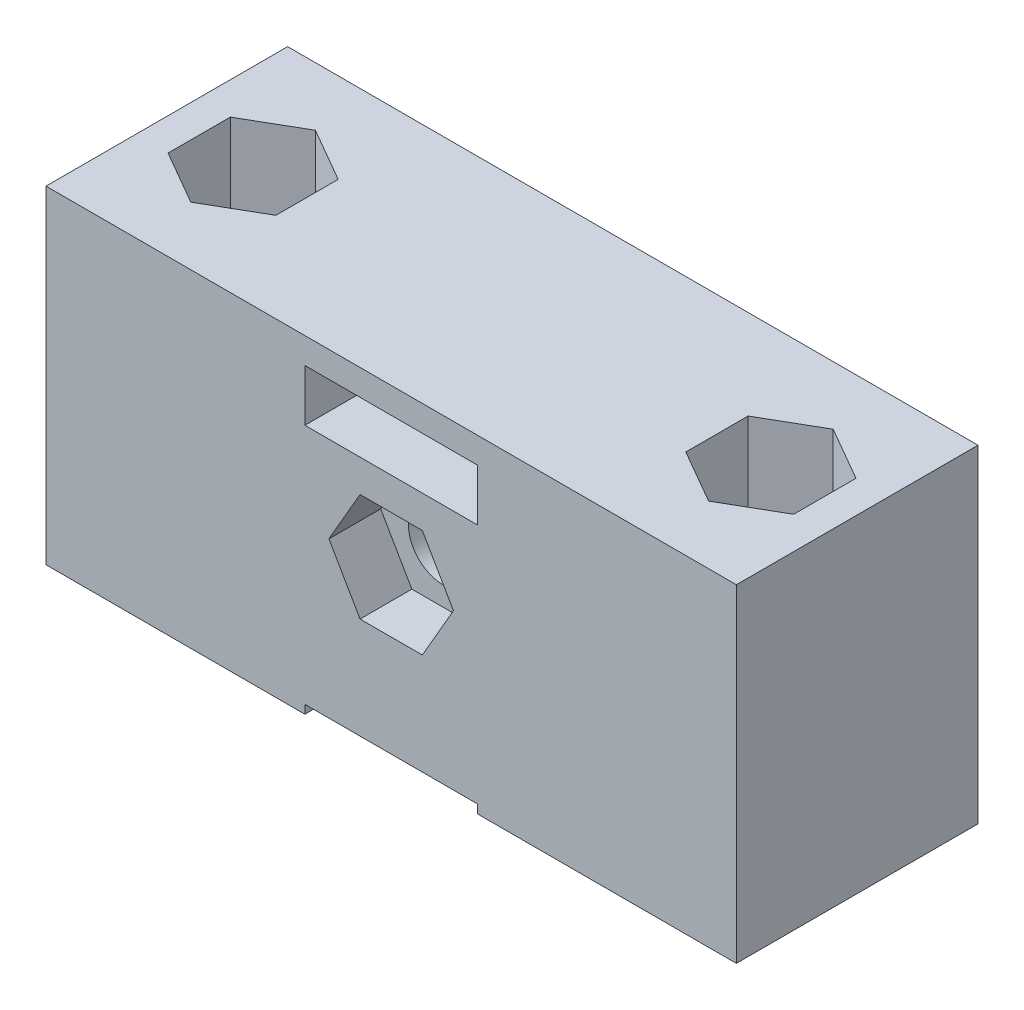
SolidWorks part; units mm, degrees
ref_plane "Front Plane" through (0, 0, 0) normal (0, 0, 1) x (1, 0, 0)
ref_plane "Top Plane" through (0, 0, 0) normal (0, 1, 0) x (1, 0, 0)
ref_plane "Right Plane" through (0, 0, 0) normal (1, 0, 0) x (0, 0, -1)
sketch "Sketch1" plane through (0, 0, 0) normal (0, 1, 0) x (1, 0, 0)
  line L1 (-20, 7) -> (20, 7)
  line L2 (-20, 7) -> (-20, -7)
  line L3 (-20, -7) -> (20, -7)
  line L4 (20, 7) -> (20, -7)
  line L5 (-20, 7) -> (20, -7) construction
  line L6 (-20, -7) -> (20, 7) construction
  point P0 (0, 0)
  dimension "D1" = 40
  dimension "D2" = 14
extrude "Boss-Extrude1" add sketch "Sketch1" along normal blind 19
sketch "Sketch2" plane through (0, 0, 7) normal (0, 0, 1) x (1, 0, 0)
  line L0 (0, 19) -> (0, 0) construction
  line L1 (-20, 19) -> (20, 19) construction
  line L3 (-5, 14.5) -> (5, 14.5)
  line L4 (-5, 14.5) -> (-5, 17.5)
  line L5 (-5, 17.5) -> (5, 17.5)
  line L6 (5, 14.5) -> (5, 17.5)
  line L7 (-5, 14.5) -> (5, 17.5) construction
  line L8 (-5, 17.5) -> (5, 14.5) construction
  line L9 (-5, -0.5) -> (5, -0.5)
  line L10 (-5, -0.5) -> (-5, 0.5)
  line L11 (-5, 0.5) -> (5, 0.5)
  line L12 (5, -0.5) -> (5, 0.5)
  line L13 (-5, -0.5) -> (5, 0.5) construction
  line L14 (-5, 0.5) -> (5, -0.5) construction
  point P5 (0, 16)
  dimension "D1" = 10
  dimension "D2" = 3
  dimension "D3" = 16
  dimension "D4" = 10
  dimension "D5" = 1
extrude "Cut-Extrude1" cut sketch "Sketch2" against normal blind 30
sketch "Sketch3" plane through (0, 0, 7) normal (0, 0, 1) x (1, 0, 0)
  line L0 (0, 19) -> (0, 0) construction
  line L1 (-20, 19) -> (20, 19) construction
  circle A0 centre (0, 9.5) radius 2
  dimension "D1" = 4
extrude "Cut-Extrude2" cut sketch "Sketch3" against normal through all
sketch "Sketch4" plane through (0, 19, 0) normal (0, 1, 0) x (1, 0, 0)
  line L0 (-20, 0) -> (20, 0) construction
  line L1 (-20, 7) -> (-20, -7) construction
  line L2 (20, -7) -> (20, 7) construction
  line L3 (0, 7) -> (0, -7) construction
  line L4 (20, 7) -> (-20, 7) construction
  line L5 (-20, -7) -> (20, -7) construction
  circle A0 centre (-15, 0) radius 1.6
  circle A1 centre (15, 0) radius 1.6
  dimension "D1" = 3.2
  dimension "D2" = 15
extrude "Cut-Extrude3" cut sketch "Sketch4" against normal through all
sketch "Sketch8" plane through (0, 0, 0) normal (0, -1, 0) x (-1, 0, 0)
  line L0 (-5, 7) -> (-5, -7) construction
  line L1 (5, -7) -> (-5, -7)
  line L2 (5, -7) -> (5, -6)
  line L3 (5, -6) -> (-5, -6)
  line L4 (-5, -7) -> (-5, -6)
  dimension "D1" = 1
extrude "Boss-Extrude2" [suppressed] add sketch "Sketch8" against normal up to next
sketch "Sketch9" plane through (0, 19, 0) normal (0, 1, 0) x (1, 0, 0)
  line L0 (0, 7) -> (0, -7) construction
  line L1 (-15, 3.6084) -> (-18.125, 1.8042)
  line L2 (-18.125, 1.8042) -> (-18.125, -1.8042)
  line L3 (-18.125, -1.8042) -> (-15, -3.6084)
  line L4 (-15, -3.6084) -> (-11.875, -1.8042)
  line L5 (-11.875, -1.8042) -> (-11.875, 1.8042)
  line L6 (-11.875, 1.8042) -> (-15, 3.6084)
  line L7 (20, 7) -> (-20, 7) construction
  line L8 (-20, -7) -> (20, -7) construction
  line L9 (11.875, 1.8042) -> (15, 3.6084)
  line L10 (11.875, -1.8042) -> (11.875, 1.8042)
  line L11 (15, -3.6084) -> (11.875, -1.8042)
  line L12 (18.125, -1.8042) -> (15, -3.6084)
  line L13 (18.125, 1.8042) -> (18.125, -1.8042)
  line L14 (15, 3.6084) -> (18.125, 1.8042)
  circle A0 centre (-15, 0) radius 3.125 construction
  circle A1 centre (15, 0) radius 3.125 construction
  dimension "D1" = 6.25
extrude "Cut-Extrude4" cut sketch "Sketch9" against normal blind 10
sketch "Sketch10" plane through (0, 0, 7) normal (0, 0, 1) x (1, 0, 0)
  line L1 (1.8042, 12.625) -> (-1.8042, 12.625)
  line L2 (-1.8042, 12.625) -> (-3.6084, 9.5)
  line L3 (-3.6084, 9.5) -> (-1.8042, 6.375)
  line L4 (-1.8042, 6.375) -> (1.8042, 6.375)
  line L5 (1.8042, 6.375) -> (3.6084, 9.5)
  line L6 (3.6084, 9.5) -> (1.8042, 12.625)
  circle A0 centre (0, 9.5) radius 3.125 construction
  dimension "D1" = 6.25
extrude "Cut-Extrude5" cut sketch "Sketch10" against normal blind 3
equation "\"X-ROD-SPACING\"=45"
equation "\"Y-ROD-SPACING\"=75"
equation "\"Z-ROD-SPACING\"=17.5"
equation "\"Y-BED-OFFSET\"=2"
equation "\"Y-BED-ROD-INSET\"=3.5"
equation "\"Y-BED-SCREW-SPACING\"=209"
equation "\"Y-BED-SCREW-CUTOUT-SLOT-HEIGHT\"=2"
equation "\"T-SLOT-NUT-FILLET-RADIUS\"=0.25"
equation "\"T-SLOT-SCREW-SHAFT-RADIUS\"=1.75"
equation "\"T-SLOT-SCREW-SHAFT-CUTOUT-LENGTH\"=10.5"
equation "\"T-SLOT-NUT-DEPTH\"=4.2"
equation "\"T-SLOT-NUT-WIDTH\"=3"
equation "\"T-SLOT-NUT-END-DISTANCE\"=8"
equation "\"ACRYLIC-THICKNESS\"=10"
equation "\"ACRYLIC-THICKNESS2\"=4.5"
equation "\"ACRYLIC-TAB-CUTOUT-SIZE\"=\"ACRYLIC-THICKNESS\"+\"ACRYLIC-TAB-TOLERANCE\"*2"
equation "\"ACRYLIC-TAB-TOLERANCE\"=.1"
equation "\"ACRYLIC-TAB-WIDTH\"=\"ACRYLIC-THICKNESS\""
equation "\"ACRYLIC-M3-HOLE\"=3.1"
equation "\"SMOOTHROD-CAP-SCREW-DISTANCE\"=20"
equation "\"FRAME-WIDTH-INNER\"=370"
equation "\"NEMA17-HOLE-SPACING\"=31"
equation "\"NEMA17-CENTRAL-CUTOUT\"=22.5"
equation "\"Z-BRACKET-REACH\"=55"
equation "\"Z-ROD-INSET\"=16"
equation "\"TOP-BRACKET-SPACING\"=40"
equation "\"SMOOTHROD-X-LENGTH\"=350"
equation "\"SMOOTHROD-Y-LENGTH\"=350"
equation "\"SMOOTHROD-Z-LENGTH\"=350"
equation "\"SMOOTHROD-TIGHTENING-HEADROOM\"=.25"
equation "\"LEADSCREW-Z-LENGTH\"=300"
equation "\"SCREW-LENGTH-FRAME\"=\"ACRYLIC-THICKNESS\" + 10"
equation "\"SCREW-LENGTH-MOTOR\"=\"ACRYLIC-THICKNESS\" + 5"
equation "\"SCREW-LENGTH-EXTRUDER\"=28"
equation "\"SCREW-HEAD-RADIUS\"=6"
equation "\"PRINTED-M3-HOLE\"=3.5"
equation "\"PRINTED-X-SMOOTHROD-DIAMETER\"=8.2"
equation "\"PRINTED-X-SMOOTHROD-CUTOUT\"=10"
equation "\"PRINTED-X-BASE-HEIGHT\"=10"
equation "\"PRINTED-LM8UU-CUTOUT-SIZE\"=15.25"
equation "\"PRINTED-LM8UU-CUTOUT-LENGTH\"=24.5"
equation "\"PRINTED-X-IDLER-HEIGHT\"=16"
equation "\"PSU-MOUNTING-WIDTH\"=95"
equation "\"PSU-MOUNTING-HEIGHT\"=177"
equation "\"Y-BELT-TO-ROD-DISTANCE\"=20"
equation "\"SPOOL-HOLDER-ROD-SPACING\"=150"
equation "\"ACRYLIC-X-CARRIAGE-WIDTH\"=55"
equation "\"ACRYLIC-X-CARRIAGE-HEIGHT\"=75"
equation "\"ACRYLIC-X-CARRIAGE-LM8UU-CUTOUT-WIDTH\"=24.25"
equation "\"ACRYLIC-X-CARRIAGE-LM8UU-CUTOUT-HEIGHT\"=11.5"
equation "\"ACRYLIC-X-CARRIAGE-SCREW-SPACING-X\"=15"
equation "\"ACRYLIC-X-CARRIAGE-SCREW-SPACING-Y\"=33"
equation "\"ACRYLIC-X-CARRIAGE-CENTER-TAB-SPACING\"=14"
equation "\"ACRYLIC-X-CARRIAGE-EXTRUDER-OFFSET\"=26"
equation "\"ACRYLIC-X-CARRIAGE-EXTRUDER-ANGLE\"=90"
equation "\"ACRYLIC-X-CARRIAGE-EXTRUDER-SHELF-DEPTH\"=\"ACRYLIC-X-CARRIAGE-EXTRUDER-OFFSET\" + 28"
equation "\"ACRYLIC-X-CARRIAGE-EXTRUDER-BRACE-SPACING\"=23"
equation "\"ACRYLIC-X-CARRIAGE-EXTRUDER-BRACE-TAB-OFFSET\"=20"
equation "\"ACRYLIC-X-CARRIAGE-EXTRUDER-BRACE-HEIGHT\"=35"
equation "\"ACRYLIC-X-CARRIAGE-EXTRUDER-BRACE-SCREW-SPACING\"=22"
equation "\"ACRYLIC-X-CARRIAGE-DUAL-WIDTH-MULTIPLIER\"=1.65"
equation "\"ACRYLIC-X-CARRIAGE-DUAL-HOTEND-SPACING\"=42"
equation "\"ACRYLIC-X-CARRIAGE-DUAL-WIDTH\"=95"
equation "\"ACRYLIC-X-CARRIAGE-DUAL-HOTEND-SEPARATION\"=35"
equation "\"ACRYLIC-X-CARRIAGE-DUAL-MOUNT-PLATE-DEPTH\"=75"
equation "\"ACRYLIC-X-CARRIAGE-DUAL-MOUNT-BRACE-WIDTH\"=33"
equation "\"ACRYLIC-X-CARRIAGE-DUAL-MOUNT-SCREW-WIDTH\"=40"
equation "\"BLOWER-FAN-WIDTH\"=15"
equation "\"PRINTED-M3-NUT-AF\"=6.25"
equation "\"D1@Sketch9\"=\"PRINTED-M3-NUT-AF\""
equation "\"D1@Sketch10\"=\"PRINTED-M3-NUT-AF\""
